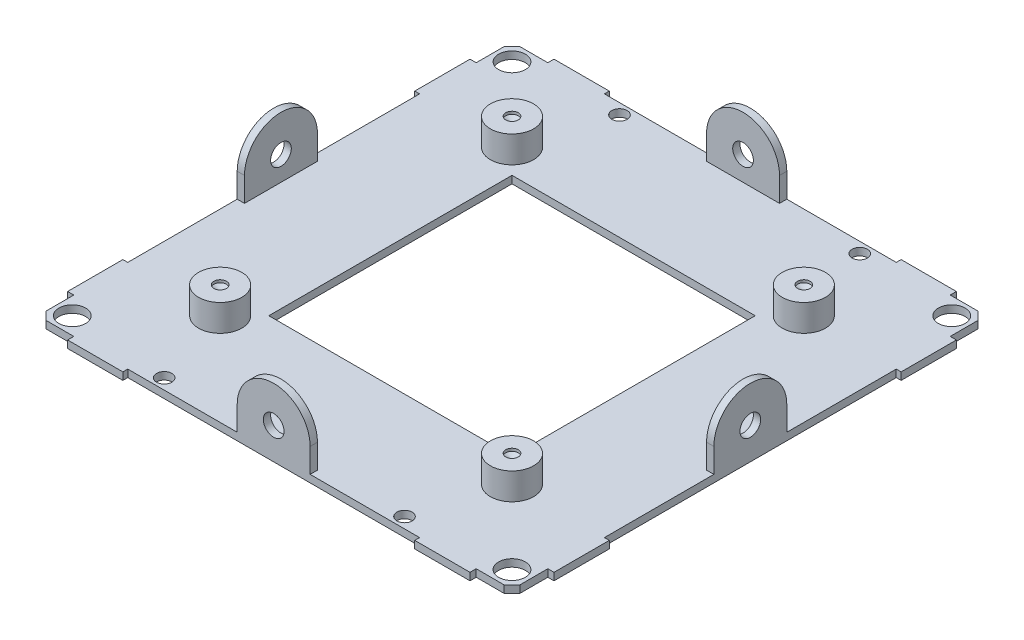
SolidWorks part; units mm, degrees
material "5052-H38"
ref_plane "Front Plane" through (0, 0, 0) normal (0, 0, 1) x (1, 0, 0)
ref_plane "Top Plane" through (0, 0, 0) normal (0, 1, 0) x (1, 0, 0)
ref_plane "Right Plane" through (0, 0, 0) normal (1, 0, 0) x (0, 0, -1)
sketch "Sketch1" plane through (0, 0, 0) normal (0, 1, 0) x (1, 0, 0)
  line L0 (-50, 50) -> (-41.364, 50)
  line L1 (-50, -50) -> (50, -50)
  line L2 (-50, -50) -> (-50, 50)
  line L3 (-50, 50) -> (50, 50)
  line L4 (50, -50) -> (50, 50)
  line L5 (-50, -50) -> (50, 50) construction
  line L6 (-50, 50) -> (50, -50) construction
  line L7 (-50, 50) -> (-50, 41.364)
  line L8 (-50, 41.364) -> (-48.73, 41.364)
  line L9 (-48.73, 41.364) -> (-48.73, 47.079)
  line L10 (-41.364, 50) -> (-41.364, 48.73)
  line L11 (-41.364, 48.73) -> (-47.079, 48.73)
  line L12 (-47.079, 48.73) -> (-48.73, 47.079)
  line L13 (-50, 50) -> (-45.2, 50) construction
  line L14 (-45.2, 50) -> (-45.2, 45.2) construction
  line L15 (50, 50) -> (50, 41.364)
  line L16 (50, 41.364) -> (48.73, 41.364)
  line L17 (48.73, 41.364) -> (48.73, 47.079)
  line L18 (48.73, 47.079) -> (47.079, 48.73)
  line L19 (41.364, 48.73) -> (47.079, 48.73)
  line L20 (41.364, 50) -> (41.364, 48.73)
  line L21 (50, 50) -> (41.364, 50)
  line L22 (50, -50) -> (41.364, -50)
  line L23 (41.364, -50) -> (41.364, -48.73)
  line L24 (41.364, -48.73) -> (47.079, -48.73)
  line L25 (47.079, -48.73) -> (48.73, -47.079)
  line L26 (48.73, -41.364) -> (48.73, -47.079)
  line L27 (50, -41.364) -> (48.73, -41.364)
  line L28 (50, -50) -> (50, -41.364)
  line L29 (-50, -50) -> (-50, -41.364)
  line L30 (-50, -41.364) -> (-48.73, -41.364)
  line L31 (-48.73, -41.364) -> (-48.73, -47.079)
  line L32 (-48.73, -47.079) -> (-47.079, -48.73)
  line L33 (-41.364, -48.73) -> (-47.079, -48.73)
  line L34 (-41.364, -50) -> (-41.364, -48.73)
  line L35 (-50, -50) -> (-41.364, -50)
  line L36 (0, -50) -> (0, 50) construction
  line L37 (-1000, 46.8) -> (49000, 46.8) construction
  line L38 (24.7, 46.8) -> (-24.7, 46.8)
  line L39 (-1000, 0) -> (49000, 0) construction
  line L41 (-25, -25) -> (25, -25)
  line L42 (-25, -25) -> (-25, 25)
  line L43 (-25, 25) -> (25, 25)
  line L44 (25, -25) -> (25, 25)
  line L45 (-25, -25) -> (25, 25) construction
  line L46 (-25, 25) -> (25, -25) construction
  circle A0 centre (-45.2, 45.2) radius 2.7503
  circle A1 centre (45.2, 45.2) radius 2.7503
  circle A2 centre (45.2, -45.2) radius 2.7503
  circle A3 centre (-45.2, -45.2) radius 2.7503
  circle A4 centre (-24.7, 46.8) radius 1.575
  circle A5 centre (24.7, 46.8) radius 1.575
  circle A6 centre (24.7, -46.8) radius 1.575
  circle A7 centre (-24.7, -46.8) radius 1.575
  point P0 (0, 0)
  point P15 (0, 46.8)
  point P45 (0, 0)
  point P46 (0, 0)
  point P48 (-24.7, 46.8)
  point P53 (0, 46.8)
  point P61 (25, 25)
  point P63 (0, 0)
  dimension "D4" = 4
  dimension "D1" = 100
  dimension "D2" = 100
  dimension "D3" = 8.636
  dimension "D5" = 3.2
  dimension "D6" = 24.7
extrude "Boss-Extrude1" add sketch "Sketch1" along normal blind 1.524 contours L37 A5 L38 A4 A0 L9 L8 L2 L30 L31 L32 L33 L34 L1 L23 L24 L25 L26 L27 L4 L16 L17 A1 A2 A3 A6 A7 region at (0, 0, -48.5858)
sketch "Sketch2" plane through (0, 1.524, 0) normal (0, 1, 0) x (1, 0, 0)
  line L0 (0, -1000) -> (0, 49000) construction
  line L1 (0, 50) -> (0, 45) construction
  line L2 (-41.364, 50) -> (41.364, 50) construction
  line L3 (-7.5, 47.5) -> (7.5, 47.5) construction
  line L4 (-7.5, 47.5) -> (7.5, 47.5)
  line L5 (-7.5, 47.5) -> (-7.5, 50)
  line L6 (7.5, 47.5) -> (7.5, 50)
  line L7 (-7.5, 50) -> (7.5, 50)
  line L8 (47.5, 7.5) -> (47.5, -7.5)
  line L9 (47.5, 7.5) -> (50, 7.5)
  line L10 (50, 7.5) -> (50, -7.5)
  line L11 (47.5, -7.5) -> (50, -7.5)
  line L12 (7.5, -47.5) -> (-7.5, -47.5)
  line L13 (7.5, -47.5) -> (7.5, -50)
  line L14 (7.5, -50) -> (-7.5, -50)
  line L15 (-7.5, -47.5) -> (-7.5, -50)
  line L16 (-47.5, -7.5) -> (-47.5, 7.5)
  line L17 (-47.5, -7.5) -> (-50, -7.5)
  line L18 (-50, -7.5) -> (-50, 7.5)
  line L19 (-47.5, 7.5) -> (-50, 7.5)
  point P10 (0, 47.5)
  point P27 (0, 0)
  dimension "D1" = 15
  dimension "D2" = 4
extrude "Boss-Extrude2" add sketch "Sketch2" along normal blind 12.476 contours L4 L5 L7 L6 | L8 L11 L10 L9 | L12 L15 L14 L13 | L16 L19 L18 L17
sketch "Sketch3" plane through (0, 0, 50) normal (0, 0, 1) x (1, 0, 0)
  line L0 (-1007.5, 1.524) -> (48992.5, 1.524) construction
  line L1 (7.5, 1.524) -> (-7.5, 1.524) construction
  line L2 (-7.5, 14) -> (-7.5, 1.524) construction
  line L3 (0, 1.524) -> (0, 6.5) construction
  line L4 (7.5, 14) -> (7.5, 1.524) construction
  line L5 (7.5, 6.5) -> (7.5, 14)
  line L6 (7.5, 14) -> (-7.5, 14)
  line L7 (-7.5, 14) -> (-7.5, 6.5)
  circle A0 centre (0, 6.5) radius 2.125
  arc A1 (-7.5, 6.5) -> (7.5, 6.5) centre (0, 6.5) cw
  line M4 (7.5, 1.524) -> (7.5, 14)
  line M5 (7.5, 14) -> (-7.5, 14)
  line M6 (-7.5, 14) -> (-7.5, 1.524)
extrude "Cut-Extrude1" cut sketch "Sketch3" against normal through all both and the other way through all contours A1 M5 M4 | A1 L6 M6 | A0 region at (5.8247, 12.3247, 50) region at (-5.8247, 12.3247, 50) region at (0, 6.5, 50)
sketch "Sketch4" plane through (-50, 0, 0) normal (-1, 0, 0) x (0, 0, 1)
  line L0 (-992.5, 1.524) -> (49007.5, 1.524) construction
  line L1 (-7.5, 1.524) -> (7.5, 1.524) construction
  line L2 (41.364, 1.524) -> (7.5, 1.524) construction
  line L3 (0, 1.524) -> (0, 6.5) construction
  line L4 (7.5, 14) -> (7.5, 1.524) construction
  line L5 (-7.5, 14) -> (-7.5, 1.524) construction
  line L6 (7.5, 6.5) -> (7.5, 14)
  line L7 (7.5, 14) -> (-7.5, 14)
  line L8 (-7.5, 14) -> (-7.5, 6.5)
  circle A0 centre (0, 6.5) radius 2.125
  arc A1 (7.5, 6.5) -> (-7.5, 6.5) centre (0, 6.5) ccw
  line M4 (7.5, 1.524) -> (7.5, 14)
  line M5 (7.5, 14) -> (-7.5, 14)
  line M6 (-7.5, 14) -> (-7.5, 1.524)
extrude "Cut-Extrude2" cut sketch "Sketch4" against normal through all both and the other way through all contours A0 | A1 M4 M5 | A1 L7 M6 region at (-50, 12.3247, 5.8247) region at (-50, 12.3247, -5.8247) region at (-50, 6.5, 0)
sketch "Sketch5" plane through (0, 0, 0) normal (0, -1, 0) x (1, 0, 0)
  line L0 (-1000, -50) -> (49000, -50) construction
  line L1 (-7.5, -50) -> (7.5, -50) construction
  line L2 (0, -1000) -> (0, 49000) construction
  line L3 (-30, -50) -> (30, -50) construction
  line L4 (-30, -50) -> (-30, -49) construction
  line L5 (-50, 30) -> (-49, 30) construction
  line L6 (-30, -49) -> (30, -49)
  line L7 (-30, -49) -> (-30, -50)
  line L8 (-30, -50) -> (30, -50)
  line L9 (30, -49) -> (30, -50)
  line L10 (-49, 30) -> (-50, 30)
  line L11 (-49, 30) -> (-49, -30)
  line L12 (-49, -30) -> (-50, -30)
  line L13 (-50, 30) -> (-50, -30)
  line L14 (30, 50) -> (30, 49) construction
  line L15 (30, 49) -> (30, 50)
  line L16 (30, 49) -> (-30, 49)
  line L17 (-30, 49) -> (-30, 50)
  line L18 (30, 50) -> (-30, 50)
  line L19 (50, -30) -> (49, -30) construction
  line L20 (49, -30) -> (50, -30)
  line L21 (49, -30) -> (49, 30)
  line L22 (49, 30) -> (50, 30)
  line L23 (50, -30) -> (50, 30)
  point P5 (0, -50)
  point P11 (0, -50)
  point P28 (0, 0)
  dimension "D1" = 4
extrude "Cut-Extrude3" cut sketch "Sketch5" against normal through all both and the other way through all
sketch "Sketch6" plane through (0, 1.524, 0) normal (0, 1, 0) x (1, 0, 0)
  circle A0 centre (30, 30) radius 4.445
  circle A1 centre (30, -30) radius 4.445
  circle A2 centre (-30, -30) radius 4.445
  circle A3 centre (-30, 30) radius 4.445
  point P0 (30, 30)
  point P12 (0, 0)
  dimension "D1" = 4
extrude "Boss-Extrude3" add sketch "Sketch6" along normal blind 5.5
hole_wizard "#5-40 Tapped Hole1" positions "Sketch7" profile "Sketch8" tap size "#5-40" standard "ANSI Inch"
sketch "Sketch7" plane through (0, 7.024, 0) normal (0, 1, 0) x (1, 0, 0)
  point P0 (-17.223, 16.8349)
  point P2 (-17.223, 16.8349)
  point P5 (-30, 30)
  point P8 (-30, -30)
  point P11 (30, -30)
  point P14 (30, 30)
sketch "Sketch8" plane through (-17.223, 7.024, -16.8349) normal (1, 0, 0) x (0, 0, 1)
  line L0 (0, 0) -> (0, 1.3245)
  line L1 (0, 1.3245) -> (1.289, 0.55)
  line L2 (1.289, 0.55) -> (1.289, 0)
  line L5 (1.289, 0) -> (0, 0)
  line L10 (0, 1.3245) -> (-1.289, 0.55) construction
  line L11 (0, -6.35) -> (0, 107.95) construction
  dimension "Tap Drill Dia." = 2.5781
  dimension "Tap Drill Depth" = 0.55
  dimension "Drill Angle" = 118
cosmetic thread "Hole Thread1" parameters "D1"=0.55, "D2"=3.175
cosmetic thread "Hole Thread2" parameters "D1"=0.55, "D2"=3.175
cosmetic thread "Hole Thread3" parameters "D1"=0.55, "D2"=3.175
cosmetic thread "Hole Thread4" parameters "D1"=0.55, "D2"=3.175
